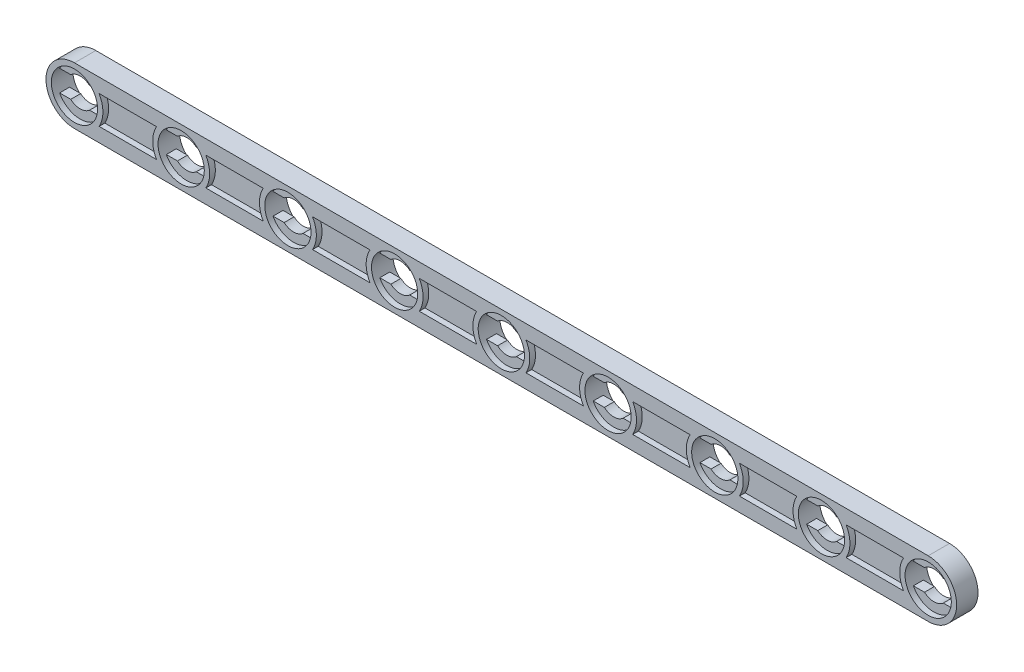
SolidWorks part; units mm, degrees
ref_plane "前视基准面" through (0, 0, 0) normal (0, 0, 1) x (1, 0, 0)
ref_plane "上视基准面" through (0, 0, 0) normal (0, 1, 0) x (1, 0, 0)
ref_plane "右视基准面" through (0, 0, 0) normal (1, 0, 0) x (0, 0, -1)
sketch "草图1" plane through (0, 0, 0) normal (0, 0, 1) x (1, 0, 0)
  line L1 (0, 4) -> (120, 4)
  line L3 (0, -4) -> (120, -4)
  arc A0 (0, 4) -> (0, -4) centre (0, 0) ccw
  arc A1 (120, -4) -> (120, 4) centre (120, 0) ccw
extrude "凸台-拉伸1" add sketch "草图1" against normal blind 3
sketch "草图2" plane through (0, 0, 0) normal (0, 0, 1) x (1, 0, 0)
  line L0 (1.3229, -1.5) -> (2.8831, -1.5)
  line L1 (-2.8831, -1.5) -> (-1.3229, -1.5)
  line L2 (1.3229, 1.5) -> (2.8831, 1.5)
  line L3 (-2.8831, 1.5) -> (-1.3229, 1.5)
  arc A0 (1.3229, 1.5) -> (-1.3229, 1.5) centre (0, 0) ccw
  arc A1 (-2.8831, 1.5) -> (-2.8831, -1.5) centre (0, 0) ccw
  arc A3 (2.8831, -1.5) -> (2.8831, 1.5) centre (0, 0) ccw
  arc A4 (-1.3229, -1.5) -> (1.3229, -1.5) centre (0, 0) ccw
extrude "切除-拉伸1" cut sketch "草图2" against normal up to next
sketch "草图3" plane through (0, 0, 0) normal (0, 0, 1) x (1, 0, 0)
  circle A1 centre (0, 0) radius 3.25
extrude "切除-拉伸2" cut sketch "草图3" against normal blind 0.8
extrude "切除-拉伸3" cut sketch "草图3<2>" along normal blind 0.8 from offset 3 offset against normal yes
sketch "草图3<2>" plane through (0, 0, 0) normal (0, 0, 1) x (1, 0, 0) same geometry as "草图3"
sketch "草图4" plane through (0, 0, 0) normal (0, 0, 1) x (1, 0, 0)
  line L1 (3.4641, 2) -> (11.5359, 2)
  line L3 (3.4641, -2) -> (11.5359, -2)
  arc A0 (11.5359, 2) -> (11.5359, -2) centre (15, 0) ccw
  arc A2 (3.4641, -2) -> (3.4641, 2) centre (0, 0) ccw
extrude "切除-拉伸4" cut sketch "草图4" against normal blind 0.8
sketch "草图5" plane through (0, 0, -3) normal (0, 0, -1) x (-1, 0, 0)
  line L1 (-4, -2) -> (-11, -2)
  line L2 (-4, -2) -> (-4, 2)
  line L3 (-4, 2) -> (-11, 2)
  line L4 (-11, -2) -> (-11, 2)
extrude "切除-拉伸6" cut sketch "草图5" against normal blind 0.8
ref_plane "基准面1" through (7.5, 0, 0) normal (1, 0, 0) x (0, 0, -1)
mirror "镜向1" about plane through (7.5, 0, 0) normal (1, 0, 0) of "切除-拉伸3", "切除-拉伸2", "切除-拉伸1"
ref_plane "基准面2" through (22.5, 0, 0) normal (1, 0, 0) x (0, 0, -1)
ref_plane "基准面3" through (15, 0, 0) normal (1, 0, 0) x (0, 0, -1)
mirror "镜向3" about plane through (15, 0, 0) normal (1, 0, 0) of "切除-拉伸6", "切除-拉伸4"
mirror "镜向4" about plane through (22.5, 0, 0) normal (1, 0, 0) of "切除-拉伸4", "切除-拉伸6"
ref_plane "基准面6" through (37.5, 0, 0) normal (1, 0, 0) x (0, 0, -1)
mirror "镜向7" about plane through (15, 0, 0) normal (1, 0, 0) of "切除-拉伸3", "切除-拉伸2", "切除-拉伸1"
mirror "镜向8" about plane through (37.5, 0, 0) normal (1, 0, 0) of "镜向7", "镜向3", "镜向1", "切除-拉伸6", "切除-拉伸4", "切除-拉伸3", "切除-拉伸2", "切除-拉伸1"
ref_plane "基准面7" through (45, 0, 0) normal (1, 0, 0) x (0, 0, -1)
mirror "镜向9" about plane through (45, 0, 0) normal (1, 0, 0) of "切除-拉伸6", "切除-拉伸4", "切除-拉伸3", "切除-拉伸2", "切除-拉伸1"
ref_plane "基准面8" through (60, 0, 0) normal (1, 0, 0) x (0, 0, -1)
mirror "镜向10" about plane through (60, 0, 0) normal (1, 0, 0) of "镜向3", "镜向1", "切除-拉伸6", "切除-拉伸4", "切除-拉伸3", "切除-拉伸2", "切除-拉伸1"
